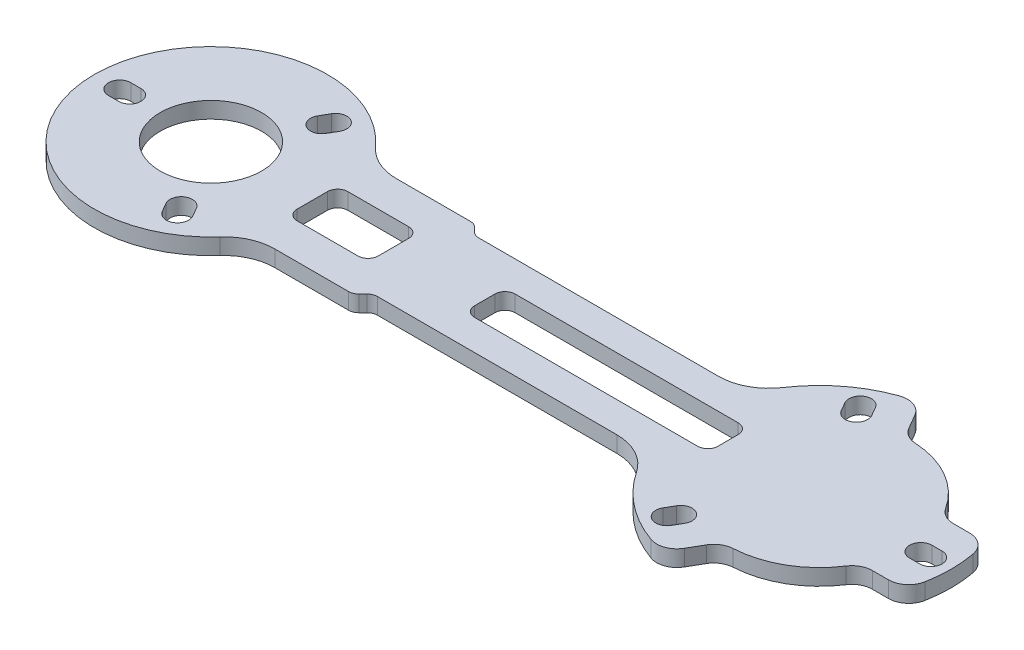
SolidWorks part; units mm, degrees
material "Thornel VCB-20 Carbon Cloth"
ref_plane "Front Plane" through (0, 0, 0) normal (0, 0, 1) x (1, 0, 0)
ref_plane "Top Plane" through (0, 0, 0) normal (0, 1, 0) x (1, 0, 0)
ref_plane "Right Plane" through (0, 0, 0) normal (1, 0, 0) x (0, 0, -1)
sketch "Sketch1" plane through (0, 0, 0) normal (0, 1, 0) x (1, 0, 0)
  line L0 (-9, 5) -> (18, 5)
  line L2 (0, 5) -> (0, -5) construction
  line L3 (-30, 0) -> (30, 0) construction
  line L4 (-20.1893, 6) -> (-10, 6)
  line L5 (-10, 6) -> (-9, 5)
  line L6 (-20.1893, -6) -> (-10, -6)
  line L7 (-10, -6) -> (-9, -5)
  line L8 (-15.0946, 6) -> (-15.0946, -6) construction
  line L9 (-9, -5) -> (18, -5)
  arc A0 (18, 5) -> (18, -5) centre (30, 0) cw
  arc A1 (-20.1893, 6) -> (-20.1893, -6) centre (-30, 0) ccw
  point P17 (-15.0946, 0)
  dimension "D1" = 10
  dimension "D3" = 23
  dimension "D4" = 26
  dimension "D2" = 60
  dimension "D5" = 45
  dimension "D6" = 45
  dimension "D7" = 12
  dimension "D8" = 10
extrude "Boss-Extrude1" add sketch "Sketch1" along normal blind 1.6
ref_axis "Axis1" through (30, -4.3921, 0) along (0, 1, 0)
ref_axis "Axis2" through (-30, -5.2731, 0) along (0, 1, 0)
sketch "Sketch2" plane through (0, 0, 0) normal (0, 1, 0) x (1, 0, 0)
  line L0 (24.75, -9.0933) -> (30, 0) construction
  line L1 (30, 0) -> (40.5, 0) construction
  line L2 (30, 0) -> (24.75, 9.0933) construction
  line L3 (40, 0) -> (41, 0) construction
  line L4 (40, 1.1) -> (41, 1.1)
  line L5 (40, -1.1) -> (41, -1.1)
  line L6 (25, -8.6603) -> (24.5, -9.5263) construction
  line L7 (25.9526, -9.2103) -> (25.4526, -10.0763)
  line L8 (24.0474, -8.1103) -> (23.5474, -8.9763)
  line L9 (25, 8.6603) -> (24.5, 9.5263) construction
  line L10 (24.0474, 8.1103) -> (23.5474, 8.9763)
  line L11 (25.9526, 9.2103) -> (25.4526, 10.0763)
  circle A3 centre (30, 0) radius 10.5 construction
  arc A4 (40, 1.1) -> (40, -1.1) centre (40, 0) ccw
  arc A5 (41, -1.1) -> (41, 1.1) centre (41, 0) ccw
  arc A6 (25.9526, -9.2103) -> (24.0474, -8.1103) centre (25, -8.6603) ccw
  arc A7 (23.5474, -8.9763) -> (25.4526, -10.0763) centre (24.5, -9.5263) ccw
  arc A8 (24.0474, 8.1103) -> (25.9526, 9.2103) centre (25, 8.6603) ccw
  arc A9 (25.4526, 10.0763) -> (23.5474, 8.9763) centre (24.5, 9.5263) ccw
  point P5 (40.5, 0)
  point P15 (24.75, -9.0933)
  point P22 (24.75, 9.0933)
  dimension "D1" = 1.1
  dimension "D2" = 21
  dimension "D3" = 120
  dimension "D4" = 120
  dimension "D5" = 1
extrude "Cut-Extrude1" cut sketch "Sketch2" along normal through all
sketch "Sketch3" plane through (0, 0, 0) normal (0, 1, 0) x (1, 0, 0)
  line L0 (-30, 0) -> (30, 0) construction
  line L1 (-38.5, 0) -> (-30, 0) construction
  line L2 (-30, 0) -> (-25.75, 7.3612) construction
  line L3 (-30, 0) -> (-25.75, -7.3612) construction
  line L4 (-26, -6.9282) -> (-25.5, -7.7942) construction
  line L5 (-25.0474, -6.3782) -> (-24.5474, -7.2442)
  line L6 (-26.9526, -7.4782) -> (-26.4526, -8.3442)
  line L7 (-38, 0) -> (-39, 0) construction
  line L8 (-38, -1.1) -> (-39, -1.1)
  line L9 (-38, 1.1) -> (-39, 1.1)
  line L10 (-26, 6.9282) -> (-25.5, 7.7942) construction
  line L11 (-26.9526, 7.4782) -> (-26.4526, 8.3442)
  line L12 (-25.0474, 6.3782) -> (-24.5474, 7.2442)
  circle A0 centre (-30, 0) radius 8.5 construction
  arc A4 (-25.0474, -6.3782) -> (-26.9526, -7.4782) centre (-26, -6.9282) ccw
  arc A5 (-26.4526, -8.3442) -> (-24.5474, -7.2442) centre (-25.5, -7.7942) ccw
  arc A6 (-38, -1.1) -> (-38, 1.1) centre (-38, 0) ccw
  arc A7 (-39, 1.1) -> (-39, -1.1) centre (-39, 0) ccw
  arc A8 (-26.9526, 7.4782) -> (-25.0474, 6.3782) centre (-26, 6.9282) ccw
  arc A9 (-24.5474, 7.2442) -> (-26.4526, 8.3442) centre (-25.5, 7.7942) ccw
  point P9 (-38.5, 0)
  point P12 (-25.75, -7.3612)
  point P24 (-25.75, 7.3612)
  dimension "D1" = 2.2
  dimension "D2" = 17
  dimension "D3" = 120
  dimension "D4" = 120
  dimension "D5" = 1
extrude "Cut-Extrude2" cut sketch "Sketch3" along normal through all
fillet "Fillet1" radius 5 4 edges at (18, 0.8, -5) (-20.1893, 0.8, -6) (-20.1893, 0.8, 6) (18, 0.8, 5)
sketch "Sketch4" plane through (0, 0, 0) normal (0, 1, 0) x (1, 0, 0)
  line L0 (-20, 0) -> (-12, 0) construction
  line L1 (-20, -2.5) -> (-12, -2.5)
  line L2 (-20, -2.5) -> (-20, 2.5)
  line L3 (-20, 2.5) -> (-12, 2.5)
  line L4 (-12, -2.5) -> (-12, 2.5)
  line L5 (-16, -2.5) -> (-16, 2.5) construction
  dimension "D1" = 8
  dimension "D2" = 5
  dimension "D3" = 16
extrude "Cut-Extrude3" cut sketch "Sketch4" along normal through all
fillet "Fillet2" radius 1 4 edges at (-12, 0.8, 2.5) (-12, 0.8, -2.5) (-20, 0.8, 2.5) (-20, 0.8, -2.5)
fillet "Fillet3" radius 1 4 edges at (-9, 0.8, -5) (-10, 0.8, -6) (-10, 0.8, 6) (-9, 0.8, 5)
sketch "Sketch5" plane through (0, 0, 0) normal (0, 1, 0) x (1, 0, 0)
  line L0 (-37.5, 12.9904) -> (-30, 0) construction
  line L1 (-30, 0) -> (-37.5, -12.9904) construction
  line L2 (-30, 0) -> (30, 0) construction
  line L3 (37, 12.1244) -> (30, 0) construction
  line L4 (30, 0) -> (37, -12.1244) construction
  circle A0 centre (-37.5, 12.9904) radius 8
  circle A1 centre (-37.5, -12.9904) radius 8
  circle A2 centre (37, -12.1244) radius 0.5
  circle A3 centre (37, 12.1244) radius 0.5
  circle A4 centre (-30, 0) radius 15 construction
  circle A5 centre (30, 0) radius 14 construction
  dimension "D5" = 16
  dimension "D6" = 30
  dimension "D7" = 28
  dimension "D8" = 1
  dimension "D1" = 120
  dimension "D2" = 120
  dimension "D3" = 120
  dimension "D4" = 120
sketch "Sketch6" plane through (0, 1.6, 0) normal (0, 1, 0) x (1, 0, 0)
  line L0 (-3, 0) -> (21, 0) construction
  line L3 (-3, 2) -> (21, 2)
  line L4 (-3, 2) -> (-3, -2)
  line L5 (-3, -2) -> (21, -2)
  line L6 (21, 2) -> (21, -2)
  line L7 (-9, 5) -> (18, 5) construction
  line L8 (-12, -1.5) -> (-12, 1.5) construction
  dimension "D2" = 9
  dimension "D1" = 9
  dimension "D3" = 3
extrude "Cut-Extrude4" cut sketch "Sketch6" against normal through all
sketch "Sketch7" plane through (0, 1.6, 0) normal (0, 1, 0) x (1, 0, 0)
  circle A0 centre (-30, 0) radius 5
  dimension "D1" = 10
extrude "Cut-Extrude5" cut sketch "Sketch7" against normal through all
fillet "Fillet4" radius 1 4 edges at (21, 0.8, -2) (21, 0.8, 2) (-3, 0.8, 2) (-3, 0.8, -2)
sketch "Sketch8" plane through (0, 1.6, 0) normal (0, 1, 0) x (1, 0, 0)
  line L0 (27.2794, 12.7121) -> (29.433, 8.9821)
  line L1 (38.0623, 4) -> (42.3693, 4)
  line L2 (30, 0) -> (24.75, 9.0933) construction
  line L3 (30, 0) -> (40.5, 0) construction
  arc A0 (29.433, 8.9821) -> (38.0623, 4) centre (30, 0) cw
  arc A2 (27.2794, 12.7121) -> (42.3693, 4) centre (30, 0) cw
  arc A3 (18, -5) -> (18, 5) centre (30, 0) ccw construction
  arc A5 (19.1908, -7.2222) -> (19.1908, 7.2222) centre (30, 0) ccw construction
  dimension "D3" = 9
  dimension "D1" = 4
  dimension "D2" = 4
extrude "Cut-Extrude6" cut sketch "Sketch8" against normal through all
pattern_circular "CirPattern1" count 2 every 120 about axis through (30, -4.3921, 0) along (0, 1, 0) of "Cut-Extrude6" reverse direction yes
fillet "Fillet5" radius 2 8 edges at (38.0623, 0.8, 4) (42.3693, 0.8, 4) (42.3693, 0.8, -4) (38.0623, 0.8, -4) (29.433, 0.8, -8.9821) (27.2794, 0.8, -12.7121) (27.2794, 0.8, 12.7121) (29.433, 0.8, 8.9821)
